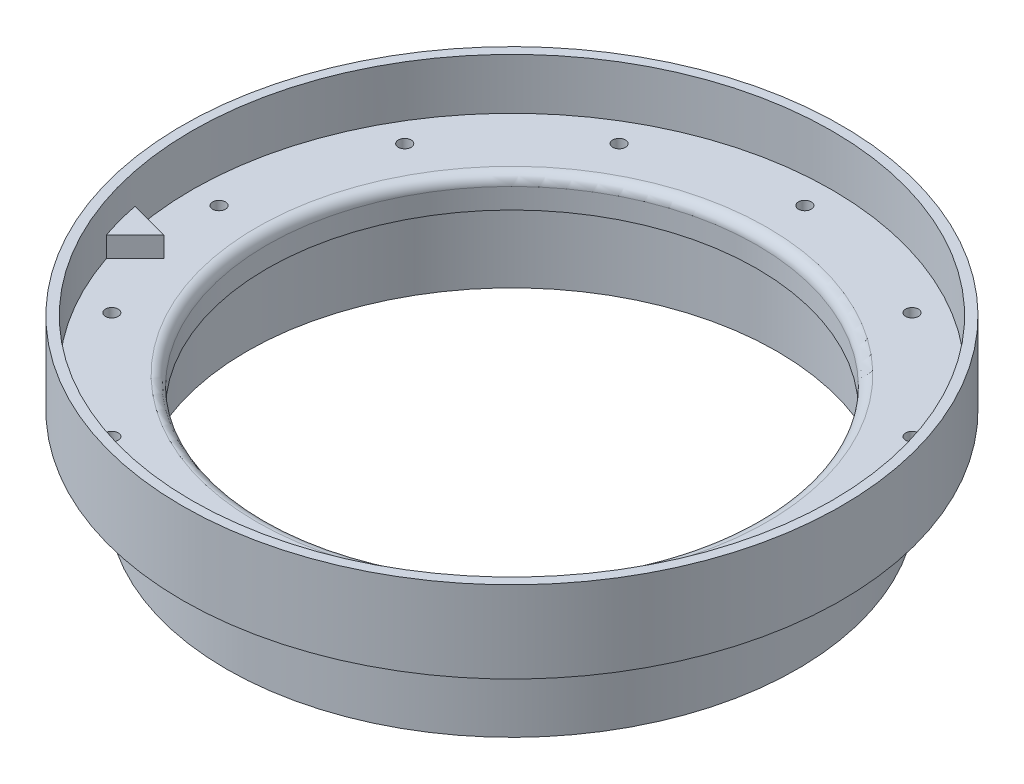
SolidWorks part; units mm, degrees
material "6061-T6 (SS)"
ref_plane "Front Plane" through (0, 0, 0) normal (0, 0, 1) x (1, 0, 0)
ref_plane "Top Plane" through (0, 0, 0) normal (0, 1, 0) x (1, 0, 0)
ref_plane "Right Plane" through (0, 0, 0) normal (1, 0, 0) x (0, 0, -1)
ref_axis "Axis1" through (0, 55, 0) along (0, -1, 0)
sketch "Cross Section" plane through (0, 0, 0) normal (0, 0, 1) x (1, 0, 0)
  line L0 (-38.1, 0) -> (-38.1, -3.175)
  line L1 (-38.1, -3.175) -> (-41.2242, -3.175)
  line L2 (-41.2242, -3.175) -> (-41.2242, -15.875)
  line L4 (0, -15.875) -> (-38.1, -15.875) construction
  line L5 (-44.3992, -15.875) -> (-44.3992, -3.175)
  line L6 (-44.3992, -3.175) -> (-51.2572, -3.175)
  line L7 (-51.2572, -3.175) -> (-51.2572, 9.525)
  line L8 (-51.2572, 9.525) -> (-49.784, 9.525)
  line L9 (-49.784, 9.525) -> (-49.784, 1.5875)
  line L11 (-38.1, 0) -> (0, 0) construction
  line L13 (-44.3992, -15.875) -> (-41.2242, -15.875)
  line L14 (-49.784, 1.5875) -> (-49.784, 3.175) construction
  line L15 (-39.6875, 1.5875) -> (-49.784, 1.5875)
  arc A0 (-39.6875, 1.5875) -> (-38.1, 0) centre (-39.6875, 0) cw
  dimension "D2" = 1.5875
  dimension "D1" = 3.1242
  dimension "D3" = 3.175
  dimension "D5" = 6.858
  dimension "D6" = 12.7
  dimension "D9" = 3.175
  dimension "D4" = 1.5875
  dimension "D7" = 38.1
revolve "Main" add sketch "Cross Section" angle 360 about axis through (0, 55, 0) along (0, -1, 0)
sketch "Hole Location" plane through (0, 0, 0) normal (0, 1, 0) x (1, 0, 0)
  line L0 (0, 0) -> (-45.5549, 0) construction
  circle A0 centre (0, 0) radius 45.5549 construction
  dimension "D1" = 91.1098
hole_wizard "#3-48 Tapped Hole1" positions "Sketch1" profile "Sketch2" tap size "#3-48" standard "ANSI Inch" end condition through all
sketch "Sketch1" plane through (0, 1.5875, 0) normal (0, 1, 0) x (1, 0, 0)
  point P0 (-45.5549, 0)
sketch "Sketch2" plane through (-45.5549, 1.5875, 0) normal (1, 0, 0) x (0, 0, 1)
  line L0 (0, 0) -> (0, 17.4625)
  line L1 (0, 17.4625) -> (0.9969, 17.4625)
  line L2 (0.9969, 17.4625) -> (0.9969, 0)
  line L5 (0.9969, 0) -> (0, 0)
  line L11 (0, -6.35) -> (0, 107.95) construction
  dimension "Thru Tap Drill Dia." = 1.9939
  dimension "Thru Tap Drill Depth" = 17.4625
cosmetic thread "Hole Thread1" parameters "D2"=2.5146
pattern_circular "CirPattern1" count 12 over 360 of "#3-48 Tapped Hole1"
sketch "Sketch3" plane through (0, 1.5875, 0) normal (0, 1, 0) x (1, 0, 0)
  line L0 (0, 0) -> (-48.0877, -12.885) construction
  line L1 (0, 0) -> (-45.5549, 0) construction
  line L2 (-47.168, -15.9256) -> (-42.6779, -11.4355)
  line L3 (-42.6779, -11.4355) -> (-48.8115, -9.792)
  circle A0 centre (0, 0) radius 49.784 construction
  circle A1 centre (0, 0) radius 49.784 construction
  arc A2 (-47.168, -15.9256) -> (-48.8115, -9.792) centre (0, 0) cw
  dimension "D1" = 15
  dimension "D2" = 60
  dimension "D3" = 6.35
extrude "Boss-Extrude1" add sketch "Sketch3" along normal blind 3.175
equation "\"D1@Hole Location\"=\"TANK DIAMETER@Cryo Tank.Assembly\"+\"GASKET SEAT THICKNESS@Cryo Tank.Assembly\"+\"LINER THICKNESS@Cryo Tank.Assembly\"+\"SHRINK FIT DELTA@Cryo Tank.Assembly\""
equation "\"D1@Cross Section\"=\"LINER THICKNESS@Cryo Tank.Assembly\"-0.002"
equation "\"D3@Cross Section\"=\"ALUMINUM LAP THICKNESS@Cryo Tank.Assembly\""
equation "\"D5@Cross Section\"=2*\"CF THICKNESS@Cryo Tank.Assembly\"+\"NOMEX THICKNESS@Cryo Tank.Assembly\""
equation "\"D7@Cross Section\"=\"TANK DIAMETER@Cryo Tank.Assembly\"/2"
